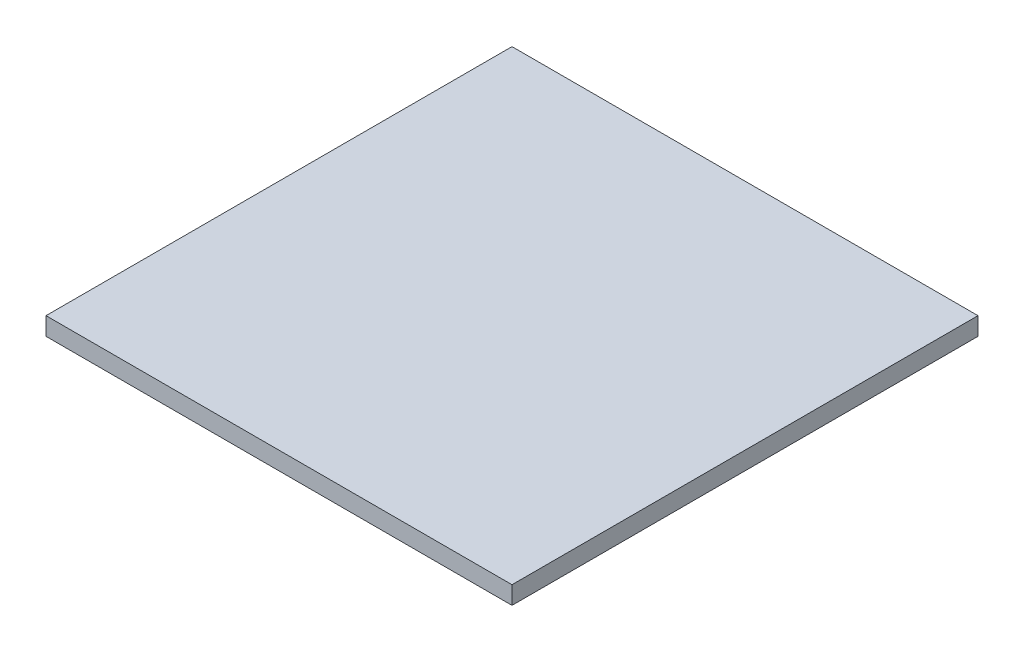
SolidWorks part; units mm, degrees
ref_plane "Front Plane" through (0, 0, 0) normal (0, 0, 1) x (1, 0, 0)
ref_plane "Top Plane" through (0, 0, 0) normal (0, 1, 0) x (1, 0, 0)
ref_plane "Right Plane" through (0, 0, 0) normal (1, 0, 0) x (0, 0, -1)
sketch "Sketch1" plane through (0, 0, 0) normal (0, 1, 0) x (1, 0, 0)
  line L1 (-65, 65) -> (65, 65)
  line L2 (-65, 65) -> (-65, -65)
  line L3 (-65, -65) -> (65, -65)
  line L4 (65, 65) -> (65, -65)
  line L5 (-65, 65) -> (65, -65) construction
  line L6 (-65, -65) -> (65, 65) construction
  point P0 (0, 0)
  dimension "D1" = 130
  dimension "D2" = 130
extrude "Boss-Extrude1" add sketch "Sketch1" along normal blind 5
